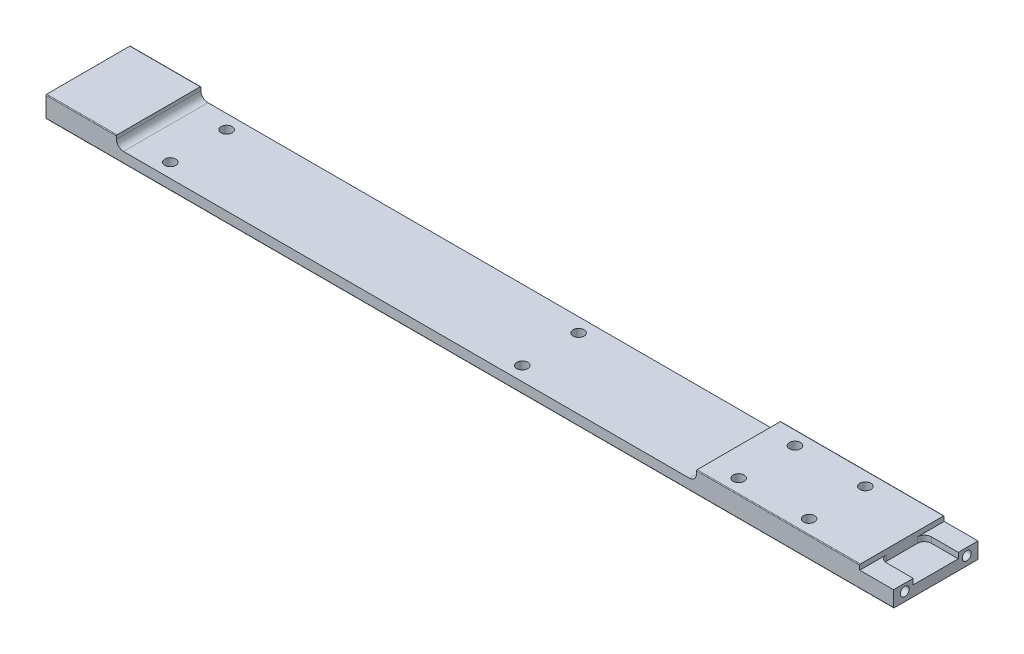
SolidWorks part; units mm, degrees
material "6061 Alloy"
ref_plane "Front Plane" through (0, 0, 0) normal (0, 0, 1) x (1, 0, 0)
ref_plane "Top Plane" through (0, 0, 0) normal (0, 1, 0) x (1, 0, 0)
ref_plane "Right Plane" through (0, 0, 0) normal (1, 0, 0) x (0, 0, -1)
sketch "Sketch1" plane through (0, 0, 0) normal (0, 1, 0) x (1, 0, 0)
  line L1 (191.135, -19.05) -> (-191.135, -19.05)
  line L2 (191.135, -19.05) -> (191.135, 19.05)
  line L3 (191.135, 19.05) -> (-191.135, 19.05)
  line L4 (-191.135, -19.05) -> (-191.135, 19.05)
  line L5 (191.135, -19.05) -> (-191.135, 19.05) construction
  line L6 (191.135, 19.05) -> (-191.135, -19.05) construction
  point P0 (0, 0)
  dimension "Length" = 382.27
  dimension "Width" = 38.1
sketch "Sketch2" plane through (0, 0, 0) normal (1, 0, 0) x (0, 0, -1)
  line L0 (19.05, 4.7625) -> (19.05, -4.7625) construction
  point P2 (19.05, 0)
  dimension "Thickness" = 9.525
sketch "Sketch3" plane through (0, 0, 0) normal (0, 1, 0) x (1, 0, 0)
  line L1 (-191.135, 19.05) -> (191.135, 19.05)
  line L2 (-191.135, 19.05) -> (-191.135, -19.05)
  line L3 (-191.135, -19.05) -> (191.135, -19.05)
  line L4 (191.135, 19.05) -> (191.135, -19.05)
extrude "Boss-Extrude1" add sketch "Sketch3" against normal up to vertex (4.7625 mm away) and the other way up to vertex (4.7625 mm away) up to point (0, -4.7625, -19.05) other way up to point (0, 4.7625, -19.05)
fillet "Fillet1" radius 0.3143 4 edges at (0, -4.7625, 19.05) (0, -4.7625, -19.05) (0, 4.7625, -19.05) (0, 4.7625, 19.05)
sketch "Sketch4" plane through (-191.135, 0, 0) normal (-1, 0, 0) x (0, 0, 1)
  line L0 (0, -0.762) -> (13.97, -0.762) construction
  line L1 (0, -0.762) -> (-13.97, -0.762) construction
  line L2 (0, -0.762) -> (0, 0) construction
  dimension "D1" = 13.97
  dimension "D2" = 13.97
  dimension "D3" = 0.762
hole_wizard "Tap Drill for #10-32 Tap1" positions "Sketch5" profile "Sketch6" hole size "#10-32" standard "ANSI Inch"
sketch "Sketch5" plane through (-191.135, 0, 0) normal (-1, 0, 0) x (0, 0, 1)
  point P0 (-13.97, -0.762)
  point P3 (13.97, -0.762)
sketch "Sketch6" plane through (-191.135, -0.762, -13.97) normal (0, 1, 0) x (0, 0, 1)
  line L0 (0, 0) -> (0, 26.6133)
  line L1 (0, 26.6133) -> (2.0193, 25.4)
  line L2 (2.0193, 25.4) -> (2.0193, 0)
  line L5 (2.0193, 0) -> (0, 0)
  line L10 (0, 26.6133) -> (-2.0193, 25.4) construction
  line L11 (0, -6.35) -> (0, 107.95) construction
  dimension "Hole Dia." = 4.0386
  dimension "Hole Depth" = 25.4
  dimension "Drill Angle" = 118
hole_wizard "Tap Drill for #10-32 Tap2" positions "Sketch7" profile "Sketch8" hole size "#10-32" standard "ANSI Inch"
sketch "Sketch7" plane through (191.135, 0, 0) normal (1, 0, 0) x (0, 0, -1)
  point P0 (-13.97, -0.762)
  point P3 (13.97, -0.762)
sketch "Sketch8" plane through (191.135, -0.762, 13.97) normal (0, 1, 0) x (0, 0, -1)
  line L0 (0, 0) -> (0, 26.6133)
  line L1 (0, 26.6133) -> (2.0193, 25.4)
  line L2 (2.0193, 25.4) -> (2.0193, 0)
  line L5 (2.0193, 0) -> (0, 0)
  line L10 (0, 26.6133) -> (-2.0193, 25.4) construction
  line L11 (0, -6.35) -> (0, 107.95) construction
  dimension "Hole Dia." = 4.0386
  dimension "Hole Depth" = 25.4
  dimension "Drill Angle" = 118
sketch "Sketch10" plane through (0, 0, -19.05) normal (0, 0, -1) x (-1, 0, 0)
  line L0 (159.385, 4.7625) -> (159.385, 3.175)
  line L1 (-191.135, 4.7625) -> (191.135, 4.7625) construction
  line L2 (156.21, 0) -> (-99.06, 0)
  line L3 (-102.235, 3.175) -> (-102.235, 4.7625)
  line L4 (-102.235, 4.7625) -> (159.385, 4.7625)
  line L5 (-191.135, -3.175) -> (-191.135, 33.0219) construction
  line L6 (191.135, -3.175) -> (191.135, 33.0219) construction
  line L7 (-191.135, 4.7625) -> (-175.895, 4.7625)
  line L8 (-175.895, 4.7625) -> (-175.895, 2.4765)
  line L9 (-175.895, 2.4765) -> (-191.135, 2.4765)
  line L10 (-191.135, -4.4482) -> (-191.135, 4.4482) construction
  line L11 (-191.135, 2.4765) -> (-191.135, 4.7625)
  arc A0 (159.385, 3.175) -> (156.21, 0) centre (156.21, 3.175) cw
  arc A1 (-99.06, 0) -> (-102.235, 3.175) centre (-99.06, 3.175) cw
  point P12 (159.385, 0)
  dimension "D4" = 3.175
  dimension "D1" = 88.9
  dimension "D2" = 31.75
  dimension "D3" = 4.7625
  dimension "D5" = 15.24
  dimension "D6" = 2.286
extrude "Cut-Extrude1" cut sketch "Sketch10" against normal through all
sketch "Sketch13" plane through (0, -4.7625, 0) normal (0, -1, 0) x (1, 0, 0)
  line L0 (191.135, 0) -> (146.685, 0) construction
  line L1 (191.135, 18.7357) -> (191.135, -18.7357) construction
  line L2 (146.685, 0) -> (146.685, 12.7) construction
  line L3 (146.685, 12.7) -> (114.935, 12.7) construction
  line L4 (114.935, 12.7) -> (114.935, -12.7) construction
  line L5 (114.935, -12.7) -> (146.685, -12.7) construction
  line L6 (146.685, -12.7) -> (146.685, 0) construction
  dimension "D1" = 44.45
  dimension "D2" = 31.75
  dimension "D3" = 31.75
hole_wizard "#10 Clearance Hole1" positions "Sketch14" profile "Sketch15" hole size "#10" standard "ANSI Inch" end condition through all
sketch "Sketch14" plane through (0, -4.7625, 0) normal (0, -1, 0) x (-1, 0, 0)
  point P0 (-114.935, 12.7)
  point P3 (-146.685, 12.7)
  point P6 (-146.685, -12.7)
  point P9 (-114.935, -12.7)
sketch "Sketch15" plane through (114.935, -4.7625, -12.7) normal (1, 0, 0) x (0, 0, -1)
  line L0 (0, 0) -> (0, 9.525)
  line L1 (0, 9.525) -> (2.4892, 9.525)
  line L2 (2.4892, 9.525) -> (2.4892, 3.1411)
  line L3 (2.4892, 3.1411) -> (5.2197, 0)
  line L5 (5.2197, 0) -> (0, 0)
  line L6 (-2.4892, 3.1411) -> (-5.2197, 0) construction
  line L11 (0, -6.35) -> (0, 107.95) construction
  dimension "Thru Hole Dia." = 4.9784
  dimension "Thru Hole Depth" = 9.525
  dimension "Near C'Sink Dia." = 10.4394
  dimension "Near C'Sink Angle" = 82
sketch "Sketch17" plane through (0, 2.4765, 0) normal (0, 1, 0) x (1, 0, 0)
  line L23 (191.135, 0) -> (191.135, 10.16)
  line L24 (191.135, -19.05) -> (191.135, 19.05) construction
  line L25 (191.135, 10.16) -> (179.07, 10.16)
  line L27 (175.895, 6.985) -> (175.895, -6.985)
  line L28 (179.07, -10.16) -> (191.135, -10.16)
  line L29 (191.135, -10.16) -> (191.135, 0)
  arc A0 (175.895, -6.985) -> (179.07, -10.16) centre (179.07, -6.985) ccw
  arc A1 (179.07, 10.16) -> (175.895, 6.985) centre (179.07, 6.985) ccw
  point P11 (175.895, 10.16)
  dimension "D2" = 3.175
  dimension "D1" = 15.24
extrude "Cut-Extrude2" cut sketch "Sketch17" against normal blind 2.54
sketch "Sketch18" plane through (0, 0, 0) normal (0, 1, 0) x (1, 0, 0)
  line L0 (30.0312, 19.05) -> (17.3312, 19.05) construction
  line L1 (99.06, 19.05) -> (-156.21, 19.05) construction
  line L2 (30.0312, 19.584) -> (30.0312, 16.7333) construction
  line L3 (17.3312, 19.05) -> (17.3312, 12.7) construction
  line L4 (17.3312, 12.7) -> (17.3312, -12.7) construction
  line L5 (17.3312, -12.7) -> (17.3312, -19.05) construction
  line L6 (99.06, -19.05) -> (-156.21, -19.05) construction
  line L7 (17.3312, -19.05) -> (-141.4188, -19.05) construction
  line L8 (-141.4188, -19.05) -> (-141.4188, -12.7) construction
  line L9 (-141.4188, -12.7) -> (-141.4188, 12.7) construction
  line L10 (-141.4188, 12.7) -> (-141.4188, 19.05) construction
  dimension "D1" = 6.35
  dimension "D2" = 25.4
  dimension "D3" = 6.35
  dimension "D4" = 25.4
hole_wizard "#10 Clearance Hole2" positions "Sketch19" profile "Sketch20" hole size "#10" standard "ANSI Inch" end condition through all
sketch "Sketch19" plane through (0, 0, 0) normal (0, 1, 0) x (1, 0, 0)
  point P0 (-141.4188, 12.7)
  point P3 (-141.4188, -12.7)
  point P6 (17.3312, 12.7)
  point P9 (17.3312, -12.7)
sketch "Sketch20" plane through (-141.4188, 0, -12.7) normal (1, 0, 0) x (0, 0, 1)
  line L0 (0, 0) -> (0, 4.7625)
  line L1 (0, 4.7625) -> (2.4892, 4.7625)
  line L2 (2.4892, 4.7625) -> (2.4892, 0)
  line L5 (2.4892, 0) -> (0, 0)
  line L11 (0, -6.35) -> (0, 107.95) construction
  dimension "Thru Hole Dia." = 4.9784
  dimension "Thru Hole Depth" = 4.7625
sketch "Sketch21" plane through (191.135, 0, 0) normal (1, 0, 0) x (0, 0, -1)
  circle A0 centre (0, 33.0219) radius 31.75 construction
equation "\"D1@Fillet1\" = \"Thickness@Sketch2\" * .033"
